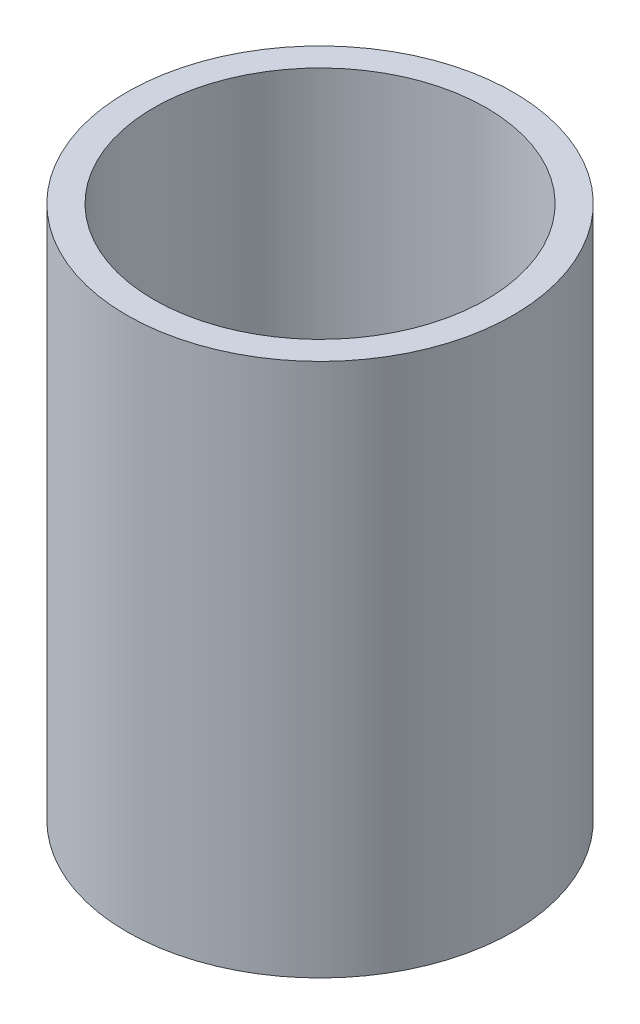
SolidWorks part; units mm, degrees
ref_plane "Front Plane" through (0, 0, 0) normal (0, 0, 1) x (1, 0, 0)
ref_plane "Top Plane" through (0, 0, 0) normal (0, 1, 0) x (1, 0, 0)
ref_plane "Right Plane" through (0, 0, 0) normal (1, 0, 0) x (0, 0, -1)
sketch "Sketch1" plane through (0, 0, 0) normal (0, 1, 0) x (1, 0, 0)
  circle A0 centre (0, 0) radius 47.5
  dimension "SLEEVE_OD" = 95
extrude "Boss-Extrude1" add sketch "Sketch1" along normal blind 131.2741
sketch "Sketch2" plane through (0, 0, 0) normal (0, 1, 0) x (1, 0, 0)
  circle A0 centre (0, 0) radius 40.8662
  dimension "BORE_D" = 81.7325
extrude "Cut-Extrude1" cut sketch "Sketch2" along normal through all
chamfer "Chamfer1" distance 3.6784 angle 60 rebuild error yes
